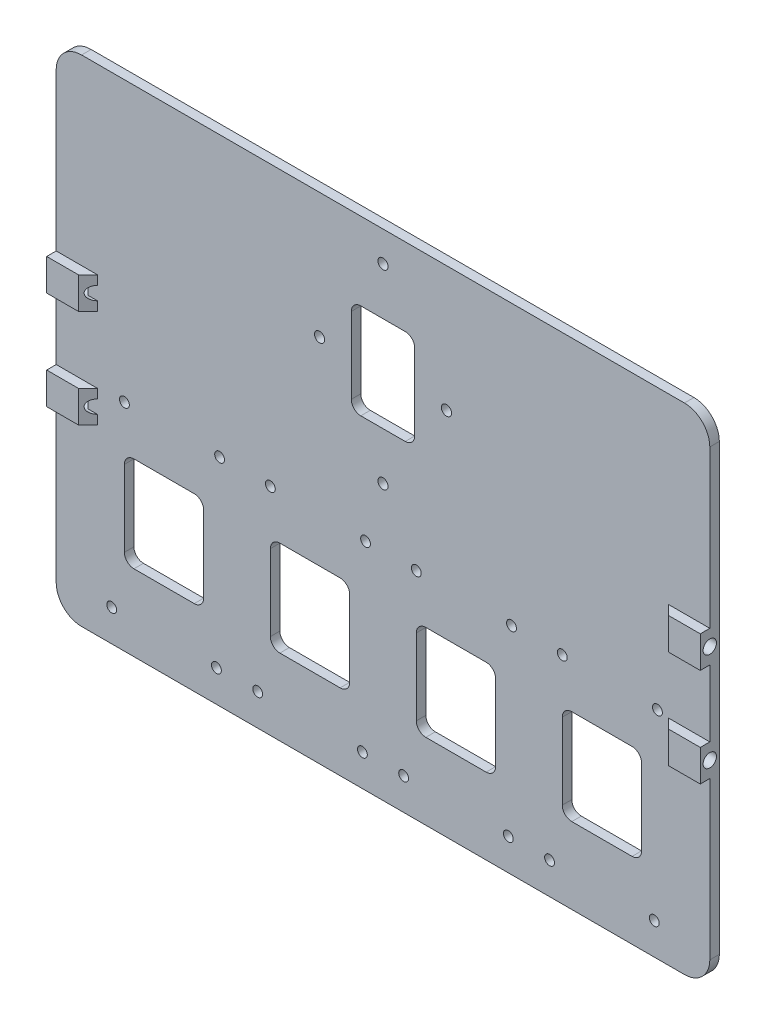
SolidWorks part; units mm, degrees
ref_plane "Front Plane" through (0, 0, 0) normal (1, 0, 0) x (0, 1, 0)
ref_plane "Top Plane" through (0, 0, 0) normal (0, 0, 1) x (0, 1, 0)
ref_plane "Right Plane" through (0, 0, 0) normal (0, 1, 0) x (-1, 0, 0)
sketch "Sketch1" plane through (0, 0, 0) normal (0, 0, 1) x (0, 1, 0)
  line L6 (0, 0) -> (31.4193, 0) construction
  line L7 (-70, -103) -> (70, -103)
  line L8 (-78, -95) -> (-78, 95)
  line L9 (-70, 103) -> (70, 103)
  line L10 (78, -95) -> (78, 95)
  line L11 (-78, -103) -> (78, 103) construction
  line L12 (-78, 103) -> (78, -103) construction
  line L13 (-68, -85.5) -> (-68, -52.5) construction
  line L15 (-10, -86.5) -> (-10, -56.5) construction
  line L23 (38.504, 27.5) -> (38.504, -27.5) construction
  line L25 (-78, 0) -> (-68, 0) construction
  line L30 (68, 0) -> (78, 0) construction
  line L34 (-73, -47.5) -> (-6, -47.5) construction
  line L35 (-73, -47.5) -> (-73, -90.5) construction
  line L40 (-73, -90.5) -> (-6, -90.5) construction
  line L41 (-6, -47.5) -> (-6, -90.5) construction
  line L42 (8.504, 20) -> (68.504, 20) construction
  line L43 (8.504, 20) -> (8.504, -20) construction
  line L44 (8.504, -20) -> (68.504, -20) construction
  line L45 (68.504, 20) -> (68.504, -20) construction
  line L46 (1.004, 27.5) -> (76.004, 27.5) construction
  line L47 (1.004, 27.5) -> (1.004, -27.5) construction
  line L48 (1.004, -27.5) -> (76.004, -27.5) construction
  line L49 (76.004, 27.5) -> (76.004, -27.5) construction
  arc A4 (70, -103) -> (78, -95) centre (70, -95) ccw
  arc A5 (-70, -103) -> (-78, -95) centre (-70, -95) cw
  arc A6 (-78, 95) -> (-70, 103) centre (-70, 95) cw
  arc A7 (70, 103) -> (78, 95) centre (70, 95) cw
  circle A8 centre (-68, -52.5) radius 1.55
  circle A9 centre (-68, -85.5) radius 1.55
  circle A10 centre (-10, -86.5) radius 1.55
  circle A11 centre (-10, -56.5) radius 1.55
  circle A24 centre (-68, -6.5) radius 1.55
  circle A25 centre (-68, -39.5) radius 1.55
  circle A26 centre (-10, -40.5) radius 1.55
  circle A27 centre (-10, -10.5) radius 1.55
  circle A28 centre (-68, 39.5) radius 1.55
  circle A29 centre (-68, 6.5) radius 1.55
  circle A30 centre (-10, 5.5) radius 1.55
  circle A31 centre (-10, 35.5) radius 1.55
  circle A32 centre (-68, 85.5) radius 1.55
  circle A33 centre (-68, 52.5) radius 1.55
  circle A34 centre (-10, 51.5) radius 1.55
  circle A35 centre (-10, 81.5) radius 1.55
  circle A40 centre (8.504, 0) radius 1.6
  circle A41 centre (38.504, 20) radius 1.6
  circle A42 centre (68.504, 0) radius 1.6
  circle A43 centre (38.504, -20) radius 1.6
  point P0 (0, 0)
  point P5 (0, 0)
  dimension "D6" = 8
  dimension "D8" = 3.1
  dimension "D19" = 3.2
  dimension "D1" = 156
  dimension "D3" = 206
  dimension "D7" = 33
  dimension "D10" = 30
  dimension "D5" = 10
  dimension "D4" = 43
  dimension "D11" = 67
  dimension "D12" = 5
  dimension "D13" = 5
  dimension "D9" = 4
  dimension "D15" = 4
  dimension "D16" = 13
  dimension "D17" = 40
  dimension "D18" = 60
  dimension "D21" = 55
  dimension "D22" = 75
  dimension "D20" = 1.996
  dimension "D14" = 4
extrude "Boss-Extrude1" add sketch "Sketch1" along normal blind 3
sketch "Sketch4" plane through (0, 0, 3) normal (0, 0, 1) x (1, 0, 0)
  line L0 (-69, -10) -> (-69, -68) construction
  line L1 (-78.5, -24) -> (-59.5, -24)
  line L2 (-81.5, -27) -> (-81.5, -51)
  line L3 (-78.5, -54) -> (-59.5, -54)
  line L4 (-56.5, -27) -> (-56.5, -51)
  line L5 (-81.5, -10) -> (-51.5, -10) construction
  line L6 (-85.5, -68) -> (-52.5, -68) construction
  line L7 (-81.5, -39) -> (-69, -39) construction
  line L8 (-35.5, -27) -> (-35.5, -51)
  line L9 (-32.5, -24) -> (-13.5, -24)
  line L10 (-32.5, -54) -> (-13.5, -54)
  line L11 (-10.5, -27) -> (-10.5, -51)
  line L12 (10.5, -27) -> (10.5, -51)
  line L13 (13.5, -24) -> (32.5, -24)
  line L14 (13.5, -54) -> (32.5, -54)
  line L15 (35.5, -27) -> (35.5, -51)
  line L16 (56.5, -27) -> (56.5, -51)
  line L17 (59.5, -24) -> (78.5, -24)
  line L18 (59.5, -54) -> (78.5, -54)
  line L19 (81.5, -27) -> (81.5, -51)
  line L20 (69, -8.2965) -> (69, -68) construction
  line L21 (52.5, -68) -> (85.5, -68) construction
  line L22 (-20, 38.504) -> (20, 38.504) construction
  line L23 (-7, 53.504) -> (7, 53.504)
  line L24 (-10, 50.504) -> (-10, 26.504)
  line L25 (-7, 23.504) -> (7, 23.504)
  line L26 (10, 50.504) -> (10, 26.504)
  line L27 (0, 68.504) -> (0, 8.504) construction
  arc A0 (78.5, -54) -> (81.5, -51) centre (78.5, -51) ccw
  arc A1 (78.5, -24) -> (81.5, -27) centre (78.5, -27) cw
  arc A2 (56.5, -27) -> (59.5, -24) centre (59.5, -27) cw
  arc A3 (56.5, -51) -> (59.5, -54) centre (59.5, -51) ccw
  arc A4 (32.5, -24) -> (35.5, -27) centre (32.5, -27) cw
  arc A5 (32.5, -54) -> (35.5, -51) centre (32.5, -51) ccw
  arc A6 (10.5, -51) -> (13.5, -54) centre (13.5, -51) ccw
  arc A7 (10.5, -27) -> (13.5, -24) centre (13.5, -27) cw
  arc A8 (-13.5, -54) -> (-10.5, -51) centre (-13.5, -51) ccw
  arc A9 (-13.5, -24) -> (-10.5, -27) centre (-13.5, -27) cw
  arc A10 (-35.5, -27) -> (-32.5, -24) centre (-32.5, -27) cw
  arc A11 (-35.5, -51) -> (-32.5, -54) centre (-32.5, -51) ccw
  arc A12 (-59.5, -54) -> (-56.5, -51) centre (-59.5, -51) ccw
  arc A13 (-81.5, -51) -> (-78.5, -54) centre (-78.5, -51) ccw
  arc A14 (-59.5, -24) -> (-56.5, -27) centre (-59.5, -27) cw
  arc A15 (-78.5, -24) -> (-81.5, -27) centre (-78.5, -27) ccw
  arc A16 (-10, 26.504) -> (-7, 23.504) centre (-7, 26.504) ccw
  arc A17 (7, 23.504) -> (10, 26.504) centre (7, 26.504) ccw
  arc A18 (7, 53.504) -> (10, 50.504) centre (7, 50.504) cw
  arc A19 (-7, 53.504) -> (-10, 50.504) centre (-7, 50.504) ccw
  point P5 (-58.5, -8.5)
  point P11 (-58.5, -8.5)
  point P67 (-56.5, -54)
  point P72 (-56.5, -24)
  point P75 (-81.5, -24)
  point P98 (10, 23.504)
  point P101 (10, 53.504)
  point P104 (-10, 53.504)
  dimension "D4" = 3
  dimension "D7" = 3
  dimension "D1" = 25
  dimension "D2" = 30
  dimension "D3" = 4
  dimension "D5" = 20
  dimension "D6" = 30
extrude "Cut-Extrude3" cut sketch "Sketch4" against normal up to next
sketch "Sketch3" plane through (103, 0, 0) normal (1, 0, 0) x (0, 1, 0)
  line L0 (0, 3) -> (0, 0) construction
  line L1 (-70, 3) -> (70, 3) construction
  line L2 (-70, 0) -> (70, 0) construction
  line L3 (-20.5, 3) -> (-10.5, 3) construction
  line L7 (-20.5, 6) -> (-10.5, 6)
  line L8 (-20.5, 6) -> (-20.5, 0)
  line L9 (-20.5, 0) -> (-10.5, 0)
  line L10 (-10.5, 6) -> (-10.5, 0)
  line L11 (10.5, 6) -> (20.5, 6)
  line L12 (10.5, 6) -> (10.5, 0)
  line L13 (10.5, 0) -> (20.5, 0)
  line L14 (20.5, 6) -> (20.5, 0)
  circle A1 centre (-15.5, 3) radius 2.1
  circle A2 centre (15.5, 3) radius 2.1
  dimension "D2" = 4.2
  dimension "D3" = 31
  dimension "D4" = 10
  dimension "D5" = 6
extrude "Boss-Extrude2" add sketch "Sketch3" against normal blind 10 contours L7 L10 L9 L8 | L11 L14 L13 L12
extrude "Boss-Extrude3" add sketch "Sketch3<4>" along normal blind 10 from surface contours L10 L9 L8 L7 | L12 L13 L14 L11 starting at face at (-103, 0, 1.5)
sketch "Sketch3<4>" plane through (103, 0, 0) normal (1, 0, 0) x (0, 1, 0) same geometry as "Sketch3"
extrude "Cut-Extrude4" cut sketch "Sketch3<6>" against normal blind 10 contours A1 | A2
sketch "Sketch3<6>" plane through (103, 0, 0) normal (1, 0, 0) x (0, 1, 0) same geometry as "Sketch3"
extrude "Cut-Extrude5" cut sketch "Sketch3<7>" along normal blind 10 from surface contours A2 | A1 starting at face at (-103, 0, 3.5)
sketch "Sketch3<7>" plane through (103, 0, 0) normal (1, 0, 0) x (0, 1, 0) same geometry as "Sketch3"
chamfer "Chamfer1" distance 3 angle 45 4 edges at (93, -19.05, 3) (93, 11.95, 3) (-93, -19.05, 3) (-93, 11.95, 3)
equation "\"MotorDriverLength\"= 60mm"
equation "\"MotorLength\"= 60"
equation "\"MotorDriverWidth\"=44"
equation "\"MotorWidth\"= 37"
equation "\"InnerWallThickness\"=3"
equation "\"BatteryWidth\"= 60"
equation "\"OuterWallThickness\" = 6"
equation "\"CompartmentHeight\"=37"
equation "\"CompartmentWidth\"= \"MotorDriverLength\""
equation "\"MotorDiameter\"=37"
equation "\"BatteryHeight\"=24.2019"
equation "\"MotorDriverHeight\"=28"
equation "\"CircuitHeight\"=30"
equation "\"FanThickness\"= 10"
equation "\"FanHeight\"=50"
equation "\"MotorShaftHole\"=12"
equation "\"BearingBore\"=10"
equation "\"MinShinWidth\"= 20"
equation "\"ShinThickness\"=10"
equation "\"PivotDistance\"=30"
equation "\"ThighLength\"= 150"
equation "\"KneeLength\" =80"
equation "\"HipBore\"=27"
equation "\"ThighThickness\"=10"
equation "\"MaxBending\"=135"
equation "\"MaxStretchingAngle\"= 50"
equation "\"ThighJointDistance\"=157.485"
equation "\"ShinLength\"=120"
equation "\"BearingDiameter\"= 10"
equation "\"CircuitLength\"=50"
equation "\"ChessisInnerWidth\"= \"OuterWallThickness\" * 2 + \"MotorDriverLength\" + \"MotorDiameter\" + \"InnerWallThickness\" * 3 + \"CircuitLength\""
equation "\"ChessisHeight\"= \"BatteryHeight\" + 10 + \"InnerWallThickness\" + \"MotorDiameter\" + 10 + \"OuterWallThickness\" * 2"
equation "\"ChassisWidth\"= \"MotorDriverWidth\"*4+30"
equation "\"D3@Sketch1\"=\"ChassisWidth\""
equation "\"D1@Sketch1\"=\"ChessisInnerWidth\"-\"OuterWallThickness\"*2"
